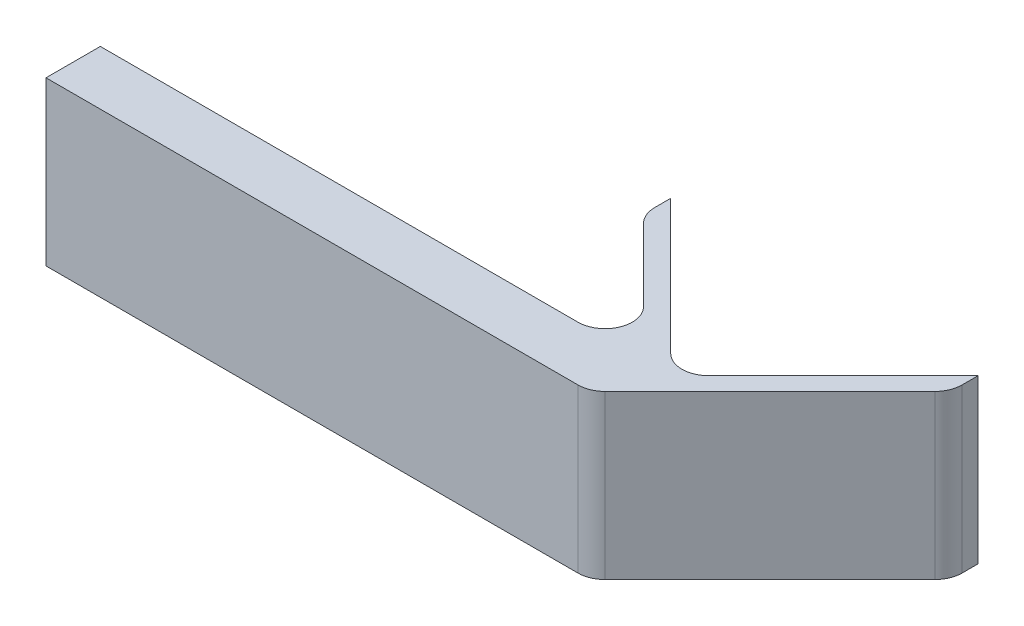
SolidWorks part; units mm, degrees
ref_plane "Front Plane" through (0, 0, 0) normal (0, 0, 1) x (1, 0, 0)
ref_plane "Top Plane" through (0, 0, 0) normal (0, 1, 0) x (1, 0, 0)
ref_plane "Right Plane" through (0, 0, 0) normal (1, 0, 0) x (0, 0, -1)
sketch "Sketch1" plane through (0, 0, 0) normal (0, 1, 0) x (1, 0, 0)
  line L0 (-73.3063, 0) -> (73.3063, 0) construction
  line L1 (30, 0) -> (-75, 0)
  line L4 (-75, 0) -> (-75, 10)
  line L5 (30, 10) -> (58.2843, 38.2843)
  line L6 (58.2843, 38.2843) -> (58.2843, 33.2843)
  line L7 (58.2843, 33.2843) -> (35, 10)
  line L8 (30, 10) -> (1.7157, 38.2843)
  line L9 (1.7157, 38.2843) -> (1.7157, 33.2843)
  line L10 (1.7157, 33.2843) -> (25, 10)
  line L11 (35, 10) -> (25, 0)
  line L12 (-75, 10) -> (25, 10)
  line L13 (25, 0) -> (-75, 0)
  point P2 (0, 0)
  point P7 (0, 0)
  point P9 (0, 0)
  point P16 (25.07, 10.0001)
  dimension "D10" = 10
  dimension "D1" = 30
  dimension "D2" = 30
  dimension "D3" = 75
  dimension "D4" = 10
  dimension "D5" = 33.2843
  dimension "D6" = 58.2843
  dimension "D7" = 225
  dimension "D8" = 33.2843
  dimension "D9" = 28.2843
  dimension "D11" = 90
  dimension "D12" = 45
  dimension "D13" = 5
extrude "Boss-Extrude3" add sketch "Sketch1" along normal blind 30 contours L4 L12 L10 L9 L8 L5 L6 L7 L11 L13
fillet "Fillet7" radius 5 1 edges at (30, 15, -10)
fillet "Fillet8" radius 5 1 edges at (25, 15, -10)
fillet "Fillet9" radius 5 2 edges at (58.2843, 15, -33.2843) (1.7157, 15, -33.2843)
fillet "Fillet10" radius 5 1 edges at (25, 15, 0)
